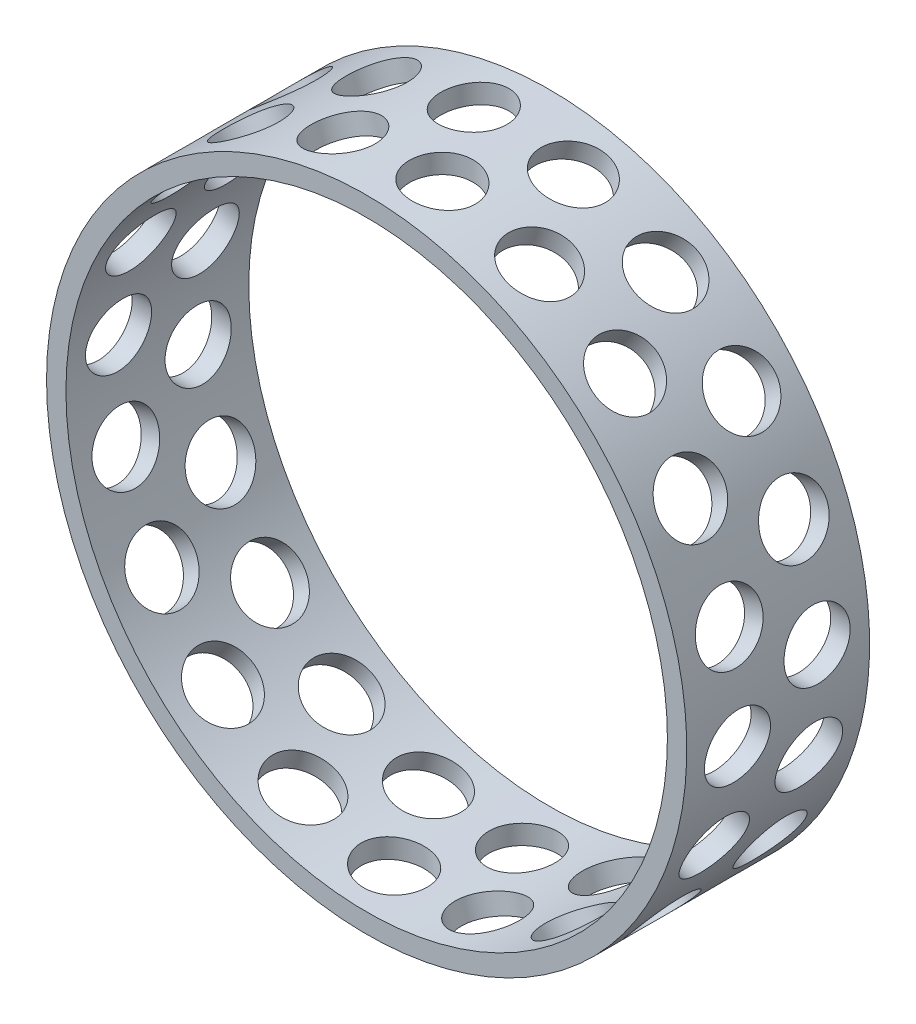
SolidWorks part; units mm, degrees
material "Plain Carbon Steel"
ref_plane "Front Plane" through (0, 0, 0) normal (0, 0, 1) x (1, 0, 0)
ref_plane "Top Plane" through (0, 0, 0) normal (0, 1, 0) x (1, 0, 0)
ref_plane "Right Plane" through (0, 0, 0) normal (1, 0, 0) x (0, 0, -1)
sketch "Sketch1" plane through (0, 0, 0) normal (1, 0, 0) x (0, 0, -1)
  line L0 (1, 82.55) -> (48.15, 82.55)
  line L1 (48.15, 82.55) -> (48.15, 77.55)
  line L2 (48.15, 77.55) -> (1, 77.55)
  line L3 (1, 77.55) -> (1, 82.55)
  dimension "D1" = 82.55
  dimension "D2" = 5
  dimension "D3" = 47.15
  dimension "D4" = 1
ref_axis "Axis1" through (0, 0, -50.5075) along (0, 0, 1)
revolve "Revolve1" add sketch "Sketch1" angle 360 about axis through (0, 0, -50.5075) along (0, 0, 1)
sketch "Sketch2" plane through (0, 0, 0) normal (1, 0, 0) x (0, 0, -1)
  line L0 (14.3098, 6.2149) -> (24.575, 0) construction
  line L1 (50.5075, 0) -> (-1.3575, 0) construction
  line L2 (24.575, 0) -> (34.8402, -6.2149) construction
  line L3 (1, 82.55) -> (1, -82.55) construction
  circle A0 centre (14.3098, 6.2149) radius 8.5
  circle A1 centre (34.8402, -6.2149) radius 8.5
  dimension "D1" = 17
  dimension "D2" = 12
  dimension "D3" = 23.575
  dimension "D4" = 31.192
extrude "Cut-Extrude1" cut sketch "Sketch2" against normal through all
pattern_circular "CirPattern1" count 20 over 360 about axis through (0, 0, -50.5075) along (0, 0, 1) of "Cut-Extrude1"
equation "\"TubeDiameter\" = 6.500in"
equation "\"D1@Sketch1\"=\"TubeDiameter\"/2"
